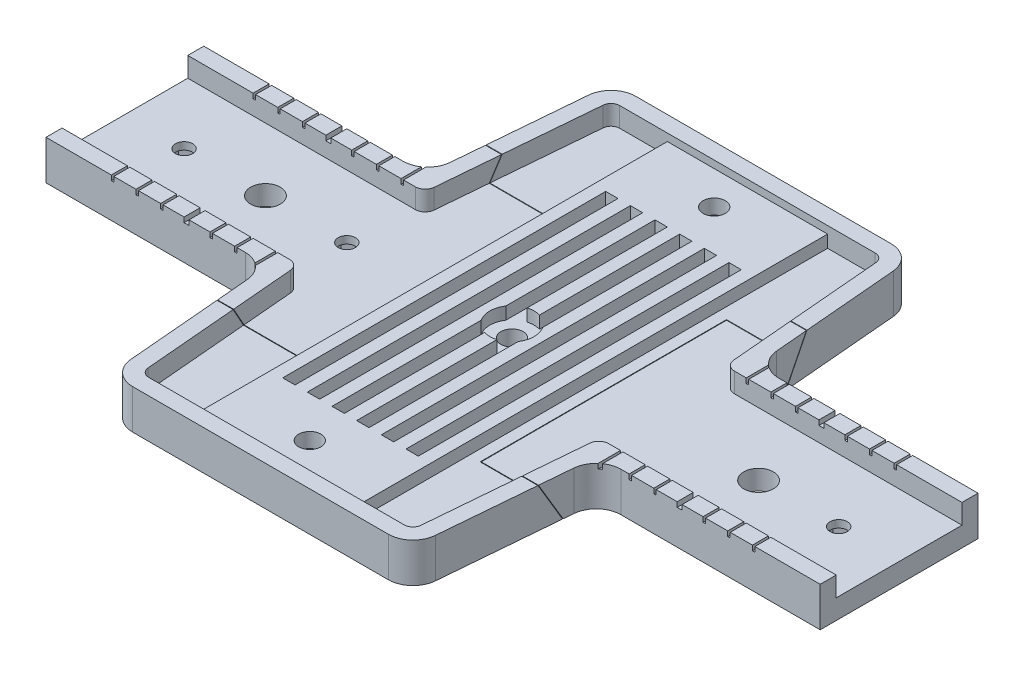
SolidWorks part; units mm, degrees
material "PBT Общее назначение"
ref_plane "Спереди" through (0, 0, 0) normal (0, 0, 1) x (1, 0, 0)
ref_plane "Сверху" through (0, 0, 0) normal (0, 1, 0) x (1, 0, 0)
ref_plane "Справа" through (0, 0, 0) normal (1, 0, 0) x (0, 0, -1)
sketch "Эскиз1" plane through (0, 0, 0) normal (0, 1, 0) x (1, 0, 0)
  line L0 (0, 0) -> (157, 0)
  line L1 (0, 0) -> (0, 32)
  line L2 (157, 0) -> (157, 32)
  line L3 (0, 32) -> (157, 32)
  dimension "D1" = 32
  dimension "D2" = 157
extrude "Бобышка-Вытянуть1" add sketch "Эскиз1" along normal blind 4
sketch "Эскиз2" plane through (0, 4, 0) normal (0, 1, 0) x (1, 0, 0)
  line L0 (0, 16) -> (157, 16) construction
  line L1 (0, 32) -> (0, 0) construction
  line L2 (157, 0) -> (157, 32) construction
  circle A0 centre (78.5, 16) radius 2.25
  dimension "D1" = 4.5
extrude "Вырез-Вытянуть1" cut sketch "Эскиз2" against normal through all
sketch "Эскиз4" plane through (0, 0, 0) normal (0, 0, 1) x (1, 0, 0)
  line L1 (78.5, 0) -> (78.5, 4) construction
  line L2 (0, 0) -> (157, 0) construction
  line L3 (0, 4) -> (157, 4) construction
  line L5 (77.25, 4) -> (79.75, 4)
  line L6 (77.25, 4) -> (77.25, 6.5)
  line L7 (79.75, 4) -> (79.75, 6.5)
  line L9 (77.25, 6.5) -> (79.75, 6.5)
  line L10 (82.25, 4) -> (84.75, 4)
  line L11 (82.25, 4) -> (82.25, 6.5)
  line L12 (84.75, 4) -> (84.75, 6.5)
  line L13 (82.25, 6.5) -> (84.75, 6.5)
  line L14 (87.25, 4) -> (89.75, 4)
  line L15 (87.25, 4) -> (87.25, 6.5)
  line L16 (89.75, 4) -> (89.75, 6.5)
  line L17 (87.25, 6.5) -> (89.75, 6.5)
  line L18 (92.25, 4) -> (94.75, 4)
  line L19 (92.25, 4) -> (92.25, 6.5)
  line L20 (94.75, 4) -> (94.75, 6.5)
  line L21 (92.25, 6.5) -> (94.75, 6.5)
  line L22 (72.25, 4) -> (74.75, 4)
  line L23 (72.25, 4) -> (72.25, 6.5)
  line L24 (74.75, 4) -> (74.75, 6.5)
  line L25 (72.25, 6.5) -> (74.75, 6.5)
  line L26 (67.25, 4) -> (69.75, 4)
  line L27 (67.25, 4) -> (67.25, 6.5)
  line L29 (69.75, 4) -> (69.75, 6.5)
  line L32 (67.25, 6.5) -> (69.75, 6.5)
  line L33 (62.25, 4) -> (64.75, 4)
  line L34 (62.25, 4) -> (62.25, 6.5)
  line L35 (64.75, 4) -> (64.75, 6.5)
  line L36 (62.25, 6.5) -> (64.75, 6.5)
  point P7 (67.5, 12)
  point P9 (85.5, 12)
  dimension "D1" = 2.5
  dimension "D2" = 2.5
  dimension "D3" = 4
  dimension "D5" = 4
  dimension "D4" = 5
  dimension "D6" = 5
extrude "Бобышка-Вытянуть3" add sketch "Эскиз4" against normal up to surface (32 mm away) up to face at (78.5, 2, -32)
ref_plane "Плоскость2" through (0, 0, 0.25) normal (0, 0, 1) x (1, 0, 0)
sketch "Эскиз7" plane through (0, 4, 0) normal (0, 1, 0) x (1, 0, 0)
  line L0 (157, 16) -> (0, 16) construction
  line L1 (157, 0) -> (157, 32) construction
  line L2 (0, 32) -> (0, 0) construction
ref_plane "Плоскость3" through (0, 0, -16) normal (0, 0, -1) x (-1, 0, 0)
sketch "Эскиз8" plane through (0, 0, 0) normal (0, -1, 0) x (1, 0, 0)
  circle A0 centre (78.5, -16) radius 2.25 construction
  circle A1 centre (78.5, -16) radius 2.25
extrude "Вырез-Вытянуть3" cut sketch "Эскиз8" against normal through all
sketch "Эскиз10" plane through (0, 4, 0) normal (0, 1, 0) x (1, 0, 0)
  line L0 (157, 0) -> (157, 3.25)
  line L1 (157, 0) -> (112, 0)
  line L2 (157, 3.25) -> (112, 3.25)
  line L3 (112, 0) -> (112, 3.25)
  line L4 (157, 0) -> (157, 32) construction
  dimension "D1" = 45
  dimension "D2" = 3.25
extrude "Бобышка-Вытянуть4" add sketch "Эскиз10" along normal blind 4
mirror "Зеркальное отражение1" about plane through (0, 0, -16) normal (0, 0, -1) of "Бобышка-Вытянуть4"
sketch "Эскиз11" plane through (0, 0, 0) normal (0, -1, 0) x (1, 0, 0)
  line L0 (140.75, 0) -> (140.75, -32) construction
  line L1 (0, 0) -> (157, 0) construction
  line L2 (157, -32) -> (0, -32) construction
  line L3 (157, 0) -> (157, -32) construction
  line L4 (16.25, 0) -> (16.25, -32) construction
  line L5 (0, -32) -> (0, 0) construction
  dimension "D1" = 16.25
  dimension "D2" = 16.25
sketch "Эскиз12" plane through (0, 6.5, 0) normal (0, 1, 0) x (1, 0, 0)
  line L0 (74.75, 32) -> (74.75, 0) construction
  line L1 (74.75, 32) -> (74.75, 0) construction
  arc A0 (79.75, 14.1292) -> (79.75, 17.8708) centre (78.5, 16) ccw construction
  arc A1 (79.75, 14.1292) -> (79.75, 17.8708) centre (78.5, 16) ccw construction
  circle A2 centre (78.5, 16) radius 4.5
  dimension "D1" = 9
extrude "Вырез-Вытянуть4" cut sketch "Эскиз12" against normal up to surface (2.5 mm away) up to face at (76.25, 4, -18.3549)
sketch "Эскиз13" plane through (0, 0, 0) normal (0, 0, 1) x (1, 0, 0)
  line L0 (78.5, 0) -> (78.5, 6.5) construction
  line L1 (0, 0) -> (157, 0) construction
  line L2 (79.75, 6.5) -> (77.25, 6.5) construction
ref_plane "Плоскость4" through (78.5, 0, 0) normal (1, 0, 0) x (0, 1, 0)
mirror "Зеркальное отражение2" about plane through (78.5, 0, 0) normal (1, 0, 0) of "Зеркальное отражение1", "Бобышка-Вытянуть4"
sketch "Эскиз14" plane through (0, 4, 0) normal (0, 1, 0) x (1, 0, 0)
  line L0 (112, 0) -> (109.392, -30.427)
  line L1 (104.4102, -35) -> (52.5898, -35)
  line L2 (47.608, -30.427) -> (45, 0)
  line L3 (94.75, 0) -> (112, 0) construction
  line L4 (45, 0) -> (112, 0)
  line L5 (78.5, 0) -> (78.5, -35) construction
  arc A0 (109.392, -30.427) -> (104.4102, -35) centre (104.4102, -30) cw
  arc A1 (52.5898, -35) -> (47.608, -30.427) centre (52.5898, -30) cw
  point P10 (78.5, -35)
  point P13 (109, -35)
  dimension "D3" = 5
  dimension "D1" = 35
  dimension "D2" = 3
extrude "Бобышка-Вытянуть5" add sketch "Эскиз14" against normal up to surface (4 mm away) up to face at (78.5, 0, -13.75)
mirror "Зеркальное отражение3" about plane through (0, 0, -16) normal (0, 0, -1) of "Бобышка-Вытянуть5"
sketch "Эскиз15" plane through (0, 4, 0) normal (0, 1, 0) x (1, 0, 0)
  line L0 (78.5, -35) -> (78.5, 67) construction
  line L1 (52.5898, -35) -> (104.4102, -35) construction
  line L2 (52.5898, 67) -> (104.4102, 67) construction
  line L6 (157, 16) -> (0, 16) construction
  line L7 (157, 16) -> (0, 16) construction
  circle A0 centre (78.5, -25) radius 2.25
  circle A1 centre (78.5, 57) radius 2.25
  dimension "D1" = 10
  dimension "D2" = 4.5
extrude "Вырез-Вытянуть5" cut sketch "Эскиз15" against normal through all
sketch "Эскиз16" plane through (78.5, 0, 0) normal (1, 0, 0) x (0, 1, 0)
  line L0 (4, 35) -> (4, 31.75)
  line L1 (4, 35) -> (8, 35)
  line L2 (4, 31.75) -> (8, 31.75)
  line L3 (8, 35) -> (8, 31.75)
  dimension "D1" = 3.25
  dimension "D2" = 4
sketch "Эскиз17" plane through (0, 4, 0) normal (0, 1, 0) x (1, 0, 0)
  line L0 (52.5898, -35) -> (104.4102, -35) construction
  line L1 (45, 0) -> (47.608, -30.427) construction
  line L2 (52.5898, -35) -> (78.5, -35)
  line L3 (44.7214, 3.25) -> (47.608, -30.427)
  line L6 (0, 3.25) -> (45, 3.25) construction
  arc A0 (47.608, -30.427) -> (52.5898, -35) centre (52.5898, -30) ccw construction
  arc A1 (47.608, -30.427) -> (52.5898, -35) centre (52.5898, -30) ccw
sweep "По траектории2" add profiles "Эскиз16" path "Эскиз17"
mirror "Зеркальное отражение4" about plane through (78.5, 0, 0) normal (1, 0, 0) of "По траектории2"
mirror "Зеркальное отражение5" about plane through (0, 0, -16) normal (0, 0, -1) of "Зеркальное отражение4", "По траектории2"
sketch "Эскиз19" plane through (0, 0, 0) normal (0, 0, 1) x (1, 0, 0)
  line L4 (82.25, 4) -> (84.75, 4)
  line L5 (84.75, 4) -> (84.75, 6.5)
  line L6 (84.75, 6.5) -> (82.25, 6.5)
  line L7 (82.25, 6.5) -> (82.25, 4)
  line L8 (82.25, 4) -> (84.75, 4)
  line L9 (84.75, 4) -> (84.75, 6.5)
  line L10 (84.75, 6.5) -> (82.25, 6.5)
  line L11 (82.25, 6.5) -> (82.25, 4)
  line L12 (72.25, 4) -> (74.75, 4)
  line L13 (74.75, 4) -> (74.75, 6.5)
  line L14 (74.75, 6.5) -> (72.25, 6.5)
  line L15 (72.25, 6.5) -> (72.25, 4)
  line L16 (72.25, 4) -> (74.75, 4)
  line L17 (74.75, 4) -> (74.75, 6.5)
  line L18 (74.75, 6.5) -> (72.25, 6.5)
  line L19 (72.25, 6.5) -> (72.25, 4)
  line L20 (92.25, 4) -> (94.75, 4)
  line L21 (94.75, 4) -> (94.75, 6.5)
  line L22 (94.75, 6.5) -> (92.25, 6.5)
  line L23 (92.25, 6.5) -> (92.25, 4)
  line L24 (92.25, 4) -> (94.75, 4)
  line L25 (94.75, 4) -> (94.75, 6.5)
  line L26 (94.75, 6.5) -> (92.25, 6.5)
  line L27 (92.25, 6.5) -> (92.25, 4)
  line L28 (87.25, 4) -> (89.75, 4)
  line L29 (87.25, 6.5) -> (87.25, 4)
  line L30 (89.75, 6.5) -> (87.25, 6.5)
  line L31 (89.75, 4) -> (89.75, 6.5)
  line L32 (87.25, 4) -> (89.75, 4)
  line L33 (87.25, 6.5) -> (87.25, 4)
  line L34 (89.75, 6.5) -> (87.25, 6.5)
  line L35 (89.75, 4) -> (89.75, 6.5)
  line L36 (77.25, 6.5) -> (77.25, 4)
  line L37 (77.25, 4) -> (79.75, 4)
  line L38 (79.75, 4) -> (79.75, 6.5)
  line L39 (79.75, 6.5) -> (77.25, 6.5)
  line L40 (77.25, 6.5) -> (77.25, 4)
  line L41 (77.25, 4) -> (79.75, 4)
  line L42 (79.75, 4) -> (79.75, 6.5)
  line L43 (79.75, 6.5) -> (77.25, 6.5)
  line L44 (62.25, 4) -> (64.75, 4)
  line L45 (64.75, 4) -> (64.75, 6.5)
  line L46 (64.75, 6.5) -> (62.25, 6.5)
  line L47 (62.25, 6.5) -> (62.25, 4)
  line L48 (62.25, 4) -> (64.75, 4)
  line L49 (64.75, 4) -> (64.75, 6.5)
  line L50 (64.75, 6.5) -> (62.25, 6.5)
  line L51 (62.25, 6.5) -> (62.25, 4)
  line L52 (67.25, 4) -> (69.75, 4)
  line L53 (69.75, 4) -> (69.75, 6.5)
  line L54 (69.75, 6.5) -> (67.25, 6.5)
  line L55 (67.25, 6.5) -> (67.25, 4)
  line L56 (67.25, 4) -> (69.75, 4)
  line L57 (69.75, 4) -> (69.75, 6.5)
  line L58 (69.75, 6.5) -> (67.25, 6.5)
  line L59 (67.25, 6.5) -> (67.25, 4)
  dimension "D1" = 0
  dimension "D2" = 0
  dimension "D3" = 0
  dimension "D4" = 0
  dimension "D5" = 0
  dimension "D6" = 0
  dimension "D7" = 0
extrude "Бобышка-Вытянуть6" add sketch "Эскиз19" along normal up to surface (31.75 mm away)
sketch "Эскиз20" plane through (0, 0, -32) normal (0, 0, -1) x (-1, 0, 0)
  line L4 (-84.75, 4) -> (-82.25, 4)
  line L5 (-84.75, 6.5) -> (-84.75, 4)
  line L6 (-82.25, 6.5) -> (-84.75, 6.5)
  line L7 (-82.25, 4) -> (-82.25, 6.5)
  line L8 (-84.75, 4) -> (-82.25, 4)
  line L9 (-84.75, 6.5) -> (-84.75, 4)
  line L10 (-82.25, 6.5) -> (-84.75, 6.5)
  line L11 (-82.25, 4) -> (-82.25, 6.5)
  line L12 (-74.75, 4) -> (-72.25, 4)
  line L13 (-74.75, 6.5) -> (-74.75, 4)
  line L14 (-72.25, 6.5) -> (-74.75, 6.5)
  line L15 (-72.25, 4) -> (-72.25, 6.5)
  line L16 (-74.75, 4) -> (-72.25, 4)
  line L17 (-74.75, 6.5) -> (-74.75, 4)
  line L18 (-72.25, 6.5) -> (-74.75, 6.5)
  line L19 (-72.25, 4) -> (-72.25, 6.5)
  line L20 (-94.75, 4) -> (-92.25, 4)
  line L21 (-94.75, 6.5) -> (-94.75, 4)
  line L22 (-92.25, 6.5) -> (-94.75, 6.5)
  line L23 (-92.25, 4) -> (-92.25, 6.5)
  line L24 (-94.75, 4) -> (-92.25, 4)
  line L25 (-94.75, 6.5) -> (-94.75, 4)
  line L26 (-92.25, 6.5) -> (-94.75, 6.5)
  line L27 (-92.25, 4) -> (-92.25, 6.5)
  line L28 (-89.75, 4) -> (-87.25, 4)
  line L29 (-87.25, 4) -> (-87.25, 6.5)
  line L30 (-87.25, 6.5) -> (-89.75, 6.5)
  line L31 (-89.75, 6.5) -> (-89.75, 4)
  line L32 (-89.75, 4) -> (-87.25, 4)
  line L33 (-87.25, 4) -> (-87.25, 6.5)
  line L34 (-87.25, 6.5) -> (-89.75, 6.5)
  line L35 (-89.75, 6.5) -> (-89.75, 4)
  line L36 (-77.25, 4) -> (-77.25, 6.5)
  line L37 (-79.75, 4) -> (-77.25, 4)
  line L38 (-79.75, 6.5) -> (-79.75, 4)
  line L39 (-77.25, 6.5) -> (-79.75, 6.5)
  line L40 (-77.25, 4) -> (-77.25, 6.5)
  line L41 (-79.75, 4) -> (-77.25, 4)
  line L42 (-79.75, 6.5) -> (-79.75, 4)
  line L43 (-77.25, 6.5) -> (-79.75, 6.5)
  line L44 (-64.75, 4) -> (-62.25, 4)
  line L45 (-64.75, 6.5) -> (-64.75, 4)
  line L46 (-62.25, 6.5) -> (-64.75, 6.5)
  line L47 (-62.25, 4) -> (-62.25, 6.5)
  line L48 (-64.75, 4) -> (-62.25, 4)
  line L49 (-64.75, 6.5) -> (-64.75, 4)
  line L50 (-62.25, 6.5) -> (-64.75, 6.5)
  line L51 (-62.25, 4) -> (-62.25, 6.5)
  line L52 (-69.75, 4) -> (-67.25, 4)
  line L53 (-69.75, 6.5) -> (-69.75, 4)
  line L54 (-67.25, 6.5) -> (-69.75, 6.5)
  line L55 (-67.25, 4) -> (-67.25, 6.5)
  line L56 (-69.75, 4) -> (-67.25, 4)
  line L57 (-69.75, 6.5) -> (-69.75, 4)
  line L58 (-67.25, 6.5) -> (-69.75, 6.5)
  line L59 (-67.25, 4) -> (-67.25, 6.5)
  dimension "D1" = 0
  dimension "D2" = 0
  dimension "D3" = 0
  dimension "D4" = 0
  dimension "D5" = 0
  dimension "D6" = 0
  dimension "D7" = 0
extrude "Бобышка-Вытянуть7" add sketch "Эскиз20" along normal up to surface (31.75 mm away)
sketch "Эскиз21" plane through (0, 4, 0) normal (0, -1, 0) x (1, 0, 0)
  circle A0 centre (78.5, 25) radius 2.25 construction
  circle A1 centre (78.5, 25) radius 2.25
  circle A2 centre (78.5, -57) radius 2.25 construction
  circle A3 centre (78.5, -57) radius 2.25
extrude "Вырез-Вытянуть6" cut sketch "Эскиз21" against normal through all
sketch "Эскиз22" plane through (0, 8, 0) normal (0, 1, 0) x (1, 0, 0)
  line L0 (106.1538, -30.1495) -> (109.0404, 3.5276) construction
  line L1 (109.0404, 3.5276) -> (112.2786, 3.25) construction
  line L3 (109.0167, 3.25) -> (109.0404, 3.5276)
  line L4 (109.0404, 3.5276) -> (112.2786, 3.25)
  line L6 (112.2786, 3.25) -> (109.0167, 3.25)
extrude "Вырез-Вытянуть7" cut sketch "Эскиз22" against normal up to surface (4 mm away) up to face at (113.9908, 4, -16)
mirror "Зеркальное отражение7" about plane through (0, 0, -16) normal (0, 0, -1) of "Вырез-Вытянуть7"
mirror "Зеркальное отражение8" about plane through (78.5, 0, 0) normal (1, 0, 0) of "Зеркальное отражение7"
sketch "Эскиз23" plane through (0, 0, 0) normal (0, -1, 0) x (1, 0, 0)
  line L2 (157, -16) -> (0, -16) construction
  circle A0 centre (28.5, -16) radius 3
  circle A1 centre (78.5, -16) radius 2.25 construction
  circle A2 centre (128.5, -16) radius 3
  dimension "D1" = 6
  dimension "D2" = 50
  dimension "D3" = 50
  dimension "D4" = 6
extrude "Вырез-Вытянуть8" cut sketch "Эскиз23" against normal through all
sketch "Эскиз24" plane through (0, 8, 0) normal (0, 1, 0) x (1, 0, 0)
  line L0 (45, 0) -> (45, 3.25)
  line L1 (0, 3.25) -> (47.9833, 3.25) construction
  line L2 (45, 3.25) -> (47.9833, 3.25)
  line L4 (52.5898, -35) -> (104.4102, -35) construction
  line L5 (104.4102, -31.75) -> (52.5898, -31.75) construction
  line L7 (50.8462, -30.1495) -> (47.9833, 3.25) construction
  line L8 (52.5898, -35) -> (104.4102, -35)
  line L9 (104.4102, -31.75) -> (52.5898, -31.75)
  line L11 (47.608, -30.427) -> (45, 0) construction
  line L12 (50.8462, -30.1495) -> (47.9833, 3.25)
  line L13 (47.608, -30.427) -> (45, 0)
  line L14 (109.392, -30.427) -> (112, 0) construction
  line L15 (106.1538, -30.1495) -> (109.0167, 3.25) construction
  line L16 (109.392, -30.427) -> (112, 0)
  line L17 (106.1538, -30.1495) -> (109.0167, 3.25)
  line L18 (157, 3.25) -> (109.0167, 3.25) construction
  line L19 (112, 3.25) -> (109.0167, 3.25)
  line L20 (112, 0) -> (112, 3.25)
  arc A0 (50.8462, -30.1495) -> (52.5898, -31.75) centre (52.5898, -30) ccw construction
  arc A1 (47.608, -30.427) -> (52.5898, -35) centre (52.5898, -30) ccw construction
  arc A2 (104.4102, -35) -> (109.392, -30.427) centre (104.4102, -30) ccw construction
  arc A3 (104.4102, -31.75) -> (106.1538, -30.1495) centre (104.4102, -30) ccw construction
  arc A4 (50.8462, -30.1495) -> (52.5898, -31.75) centre (52.5898, -30) ccw
  arc A5 (47.608, -30.427) -> (52.5898, -35) centre (52.5898, -30) ccw
  arc A6 (104.4102, -35) -> (109.392, -30.427) centre (104.4102, -30) ccw
  arc A7 (104.4102, -31.75) -> (106.1538, -30.1495) centre (104.4102, -30) ccw
extrude "Вырез-Вытянуть9" cut sketch "Эскиз24" against normal blind 2
mirror "Зеркальное отражение9" about plane through (0, 0, -16) normal (0, 0, -1) of "Вырез-Вытянуть9"
sketch "Эскиз25" plane through (0, 0, 0) normal (0, -1, 0) x (1, 0, 0)
  line L0 (78.5, 25) -> (82.5415, 25) construction
  line L1 (74.4585, 25) -> (76.4793, 21.5)
  line L2 (76.4793, 21.5) -> (80.5207, 21.5)
  line L3 (80.5207, 21.5) -> (82.5415, 25)
  line L4 (82.5415, 25) -> (80.5207, 28.5)
  line L5 (80.5207, 28.5) -> (76.4793, 28.5)
  line L6 (76.4793, 28.5) -> (74.4585, 25)
  circle A0 centre (78.5, 25) radius 3.5 construction
  dimension "D1" = 7
extrude "Вырез-Вытянуть10" cut sketch "Эскиз25" against normal blind 3.5
sketch "Эскиз26" plane through (0, 4, 0) normal (0, 1, 0) x (1, 0, 0)
  circle A0 centre (78.5, -25) radius 4
  arc A1 (79.75, -26.8708) -> (79.75, -23.1292) centre (78.5, -25) ccw construction
  arc A2 (79.75, -26.8708) -> (79.75, -23.1292) centre (78.5, -25) ccw construction
  circle A3 centre (78.5, -25) radius 2.25
  circle A4 centre (78.5, 57) radius 4
  arc A5 (77.25, 58.8708) -> (77.25, 55.1292) centre (78.5, 57) ccw construction
  arc A6 (77.25, 58.8708) -> (77.25, 55.1292) centre (78.5, 57) ccw construction
  circle A7 centre (78.5, 57) radius 2.25
  dimension "D1" = 8
  dimension "D2" = 8
extrude "Бобышка-Вытянуть8" add sketch "Эскиз26" along normal up to surface (2.5 mm away) up to face at (78.5, 6.5, 5.6755)
fillet "Скругление3" radius 1 4 edges at (74.75, 5.25, 23.6081) (74.75, 5.25, 26.3919) (82.25, 5.25, 23.6081) (82.25, 5.25, 26.3919)
fillet "Скругление4" radius 1 2 edges at (82.25, 5.25, -55.6081) (74.75, 5.25, -55.6081)
mirror "Зеркальное отражение12" about plane through (0, 0, -16) normal (0, 0, -1) of "Вырез-Вытянуть10"
sketch "Эскиз27" plane through (0, 4, 0) normal (0, 1, 0) x (1, 0, 0)
  line L0 (157, 16) -> (0, 16) construction
  line L1 (157, 3.25) -> (157, 28.75) construction
  circle A1 centre (45, 16) radius 1.75
  circle A3 centre (12, 16) radius 1.75
  circle A5 centre (144.75, 16) radius 1.75
  circle A6 centre (28.5, 16) radius 3 construction
  dimension "D1" = 3.5
  dimension "D2" = 3.5
  dimension "D3" = 16.5
  dimension "D4" = 33
  dimension "D5" = 3.5
  dimension "D6" = 12.25
extrude "Вырез-Вытянуть11" cut sketch "Эскиз27" against normal through all
sketch "Эскиз28" plane through (0, 0, 0) normal (0, -1, 0) x (1, 0, 0)
  line L0 (12, -16) -> (12, -12.8246) construction
  line L1 (12, -19.1754) -> (14.75, -17.5877)
  line L2 (14.75, -17.5877) -> (14.75, -14.4123)
  line L3 (14.75, -14.4123) -> (12, -12.8246)
  line L4 (12, -12.8246) -> (9.25, -14.4123)
  line L5 (9.25, -14.4123) -> (9.25, -17.5877)
  line L6 (9.25, -17.5877) -> (12, -19.1754)
  line L7 (45, -19.1754) -> (47.75, -17.5877)
  line L8 (47.75, -17.5877) -> (47.75, -14.4123)
  line L9 (47.75, -14.4123) -> (45, -12.8246)
  line L10 (45, -12.8246) -> (42.25, -14.4123)
  line L11 (42.25, -14.4123) -> (42.25, -17.5877)
  line L12 (42.25, -17.5877) -> (45, -19.1754)
  line L13 (45, -16) -> (45, -12.8246) construction
  line L14 (144.75, -16) -> (144.75, -12.8246) construction
  line L15 (144.75, -19.1754) -> (147.5, -17.5877)
  line L16 (147.5, -17.5877) -> (147.5, -14.4123)
  line L17 (147.5, -14.4123) -> (144.75, -12.8246)
  line L18 (144.75, -12.8246) -> (142, -14.4123)
  line L19 (142, -14.4123) -> (142, -17.5877)
  line L20 (142, -17.5877) -> (144.75, -19.1754)
  circle A0 centre (12, -16) radius 2.75 construction
  circle A1 centre (45, -16) radius 2.75 construction
  circle A2 centre (144.75, -16) radius 2.75 construction
  dimension "D1" = 5.5
  dimension "D2" = 5.5
  dimension "D3" = 5.5
extrude "Вырез-Вытянуть12" cut sketch "Эскиз28" against normal blind 2.5
sketch "Sketch2" plane through (0, 8, 0) normal (0, 1, 0) x (1, 0, 0)
  line L0 (28.5, 16) -> (28.5, 0) construction
  line L1 (45, 0) -> (0, 0) construction
  line L2 (28, 0) -> (29, 0)
  line L3 (28, 0) -> (28, 3.25)
  line L4 (29, 0) -> (29, 3.25)
  line L5 (28, 3.25) -> (29, 3.25)
  line L6 (0, 3.25) -> (47.9833, 3.25) construction
  line L7 (33.25, 3.25) -> (33.75, 3.25)
  line L8 (33.25, 3.25) -> (33.25, 0)
  line L9 (33.75, 3.25) -> (33.75, 0)
  line L10 (33.25, 0) -> (33.75, 0)
  line L11 (0, 3.25) -> (45, 3.25) construction
  line L12 (33.5, 3.25) -> (33.5, 0) construction
  line L13 (38.25, 3.25) -> (38.75, 3.25)
  line L14 (38.25, 3.25) -> (38.25, 0)
  line L15 (38.75, 3.25) -> (38.75, 0)
  line L16 (38.25, 0) -> (38.75, 0)
  line L17 (38.5, 3.25) -> (38.5, 0) construction
  line L18 (43.25, 3.25) -> (43.75, 3.25)
  line L19 (43.25, 3.25) -> (43.25, 0)
  line L20 (43.75, 3.25) -> (43.75, 0)
  line L21 (43.25, 0) -> (43.75, 0)
  line L22 (43.5, 3.25) -> (43.5, 0) construction
  line L23 (13.5, 3.25) -> (13.5, 0) construction
  line L24 (18.5, 3.25) -> (18.5, 0) construction
  line L25 (23.5, 3.25) -> (23.5, 0) construction
  line L26 (13.75, 0) -> (13.25, 0)
  line L27 (13.25, 3.25) -> (13.25, 0)
  line L28 (13.75, 3.25) -> (13.75, 0)
  line L29 (13.75, 3.25) -> (13.25, 3.25)
  line L30 (18.75, 0) -> (18.25, 0)
  line L31 (18.25, 3.25) -> (18.25, 0)
  line L32 (18.75, 3.25) -> (18.75, 0)
  line L33 (18.75, 3.25) -> (18.25, 3.25)
  line L34 (23.75, 0) -> (23.25, 0)
  line L35 (23.25, 3.25) -> (23.25, 0)
  line L36 (23.75, 3.25) -> (23.75, 0)
  line L37 (23.75, 3.25) -> (23.25, 3.25)
  circle A0 centre (28.5, 16) radius 3 construction
  circle A1 centre (28.5, 16) radius 3 construction
  dimension "D1" = 1
  dimension "D2" = 0.5
  dimension "D3" = 5
  dimension "D5" = 5
  dimension "D4" = 3
extrude "Cut-Extrude2" cut sketch "Sketch2" against normal blind 1
mirror "Mirror2" about plane through (78.5, 0, 0) normal (1, 0, 0) of "Cut-Extrude2"
mirror "Mirror3" about plane through (0, 0, -16) normal (0, 0, -1) of "Cut-Extrude2"
mirror "Mirror4" about plane through (0, 0, -16) normal (0, 0, -1) of "Mirror2"
sketch "Эскиз29" plane through (0, 0, 0) normal (-1, 0, 0) x (0, 0, 1)
  line L8 (-32, 0) -> (0, 0)
  line L9 (0, 0) -> (0, 8)
  line L10 (0, 8) -> (-3.25, 8)
  line L11 (-3.25, 8) -> (-3.25, 4)
  line L12 (-3.25, 4) -> (-28.75, 4)
  line L13 (-28.75, 4) -> (-28.75, 8)
  line L14 (-28.75, 8) -> (-32, 8)
  line L15 (-32, 8) -> (-32, 0)
  line L16 (-32, 0) -> (0, 0)
  line L17 (0, 0) -> (0, 8)
  line L18 (0, 8) -> (-3.25, 8)
  line L19 (-3.25, 8) -> (-3.25, 4)
  line L20 (-3.25, 4) -> (-28.75, 4)
  line L21 (-28.75, 4) -> (-28.75, 8)
  line L22 (-28.75, 8) -> (-32, 8)
  line L23 (-32, 8) -> (-32, 0)
  dimension "D1" = 0
sketch "Эскиз30" plane through (157, 0, 0) normal (1, 0, 0) x (0, 0, -1)
  line L8 (0, 0) -> (32, 0)
  line L9 (32, 0) -> (32, 8)
  line L10 (32, 8) -> (28.75, 8)
  line L11 (28.75, 8) -> (28.75, 4)
  line L12 (28.75, 4) -> (3.25, 4)
  line L13 (3.25, 4) -> (3.25, 8)
  line L14 (3.25, 8) -> (0, 8)
  line L15 (0, 8) -> (0, 0)
  line L16 (0, 0) -> (32, 0)
  line L17 (32, 0) -> (32, 8)
  line L18 (32, 8) -> (28.75, 8)
  line L19 (28.75, 8) -> (28.75, 4)
  line L20 (28.75, 4) -> (3.25, 4)
  line L21 (3.25, 4) -> (3.25, 8)
  line L22 (3.25, 8) -> (0, 8)
  line L23 (0, 8) -> (0, 0)
  dimension "D1" = 0
sketch "Эскиз32" plane through (0, 6.5, 0) normal (0, 1, 0) x (1, 0, 0)
  line L0 (62.25, 63.75) -> (62.25, -31.75) construction
  line L1 (62.25, 63.75) -> (62.25, 48.75)
  line L2 (94.75, 63.75) -> (94.75, -31.75) construction
  line L3 (94.75, 63.75) -> (94.75, 48.75)
  line L4 (62.25, 63.75) -> (94.75, 63.75)
  line L5 (62.25, 48.75) -> (94.75, 48.75)
  circle A0 centre (78.5, 57) radius 2.25 construction
  circle A1 centre (78.5, 57) radius 2.25
  dimension "D1" = 15
extrude "Бобышка-Вытянуть9" add sketch "Эскиз32" against normal up to surface (2.5 mm away) up to face at (144.75, 4, -14.25)
mirror "Зеркальное отражение13" about plane through (0, 0, -16) normal (0, 0, -1) of "Бобышка-Вытянуть9"
sketch "Эскиз33" plane through (0, 6, 0) normal (0, 1, 0) x (1, 0, 0)
  line L14 (47.608, 62.427) -> (45, 32)
  line L16 (45, 32) -> (45, 28.75)
  line L17 (45, 28.75) -> (47.9833, 28.75)
  line L18 (47.9833, 28.75) -> (50.8462, 62.1495)
  line L19 (52.5898, 63.75) -> (62.25, 63.75)
  line L20 (62.25, 63.75) -> (94.75, 63.75)
  line L21 (94.75, 63.75) -> (104.4102, 63.75)
  line L22 (106.1538, 62.1495) -> (109.0167, 28.75)
  line L23 (109.0167, 28.75) -> (112, 28.75)
  line L24 (112, 28.75) -> (112, 32)
  line L26 (112, 32) -> (109.392, 62.427)
  line L27 (104.4102, 67) -> (52.5898, 67)
  line L28 (47.608, 62.427) -> (45, 32)
  line L30 (45, 32) -> (45, 28.75)
  line L31 (45, 28.75) -> (47.9833, 28.75)
  line L32 (47.9833, 28.75) -> (50.8462, 62.1495)
  line L33 (52.5898, 63.75) -> (62.25, 63.75)
  line L34 (62.25, 63.75) -> (94.75, 63.75)
  line L35 (94.75, 63.75) -> (104.4102, 63.75)
  line L36 (106.1538, 62.1495) -> (109.0167, 28.75)
  line L37 (109.0167, 28.75) -> (112, 28.75)
  line L38 (112, 28.75) -> (112, 32)
  line L40 (112, 32) -> (109.392, 62.427)
  line L41 (104.4102, 67) -> (52.5898, 67)
  arc A7 (52.5898, 63.75) -> (50.8462, 62.1495) centre (52.5898, 62) ccw
  arc A8 (106.1538, 62.1495) -> (104.4102, 63.75) centre (104.4102, 62) ccw
  arc A10 (109.392, 62.427) -> (104.4102, 67) centre (104.4102, 62) ccw
  arc A11 (52.5898, 67) -> (47.608, 62.427) centre (52.5898, 62) ccw
  arc A13 (52.5898, 63.75) -> (50.8462, 62.1495) centre (52.5898, 62) ccw
  arc A14 (106.1538, 62.1495) -> (104.4102, 63.75) centre (104.4102, 62) ccw
  arc A16 (109.392, 62.427) -> (104.4102, 67) centre (104.4102, 62) ccw
  arc A17 (52.5898, 67) -> (47.608, 62.427) centre (52.5898, 62) ccw
  dimension "D1" = 0
extrude "Бобышка-Вытянуть10" add sketch "Эскиз33" along normal up to surface (2 mm away) up to face at (41, 8, -30.375)
sketch "Эскиз34" plane through (0, 6, 0) normal (0, 1, 0) x (1, 0, 0)
  line L14 (45, 3.25) -> (45, 0)
  line L16 (45, 0) -> (47.608, -30.427)
  line L17 (52.5898, -35) -> (104.4102, -35)
  line L18 (109.392, -30.427) -> (112, 0)
  line L20 (112, 0) -> (112, 3.25)
  line L21 (112, 3.25) -> (109.0167, 3.25)
  line L22 (109.0167, 3.25) -> (106.1538, -30.1495)
  line L23 (104.4102, -31.75) -> (94.75, -31.75)
  line L24 (94.75, -31.75) -> (62.25, -31.75)
  line L25 (62.25, -31.75) -> (52.5898, -31.75)
  line L26 (50.8462, -30.1495) -> (47.9833, 3.25)
  line L27 (47.9833, 3.25) -> (45, 3.25)
  line L28 (45, 3.25) -> (45, 0)
  line L30 (45, 0) -> (47.608, -30.427)
  line L31 (52.5898, -35) -> (104.4102, -35)
  line L32 (109.392, -30.427) -> (112, 0)
  line L34 (112, 0) -> (112, 3.25)
  line L35 (112, 3.25) -> (109.0167, 3.25)
  line L36 (109.0167, 3.25) -> (106.1538, -30.1495)
  line L37 (104.4102, -31.75) -> (94.75, -31.75)
  line L38 (94.75, -31.75) -> (62.25, -31.75)
  line L39 (62.25, -31.75) -> (52.5898, -31.75)
  line L40 (50.8462, -30.1495) -> (47.9833, 3.25)
  line L41 (47.9833, 3.25) -> (45, 3.25)
  arc A7 (47.608, -30.427) -> (52.5898, -35) centre (52.5898, -30) ccw
  arc A8 (104.4102, -35) -> (109.392, -30.427) centre (104.4102, -30) ccw
  arc A10 (104.4102, -31.75) -> (106.1538, -30.1495) centre (104.4102, -30) ccw
  arc A11 (50.8462, -30.1495) -> (52.5898, -31.75) centre (52.5898, -30) ccw
  arc A13 (47.608, -30.427) -> (52.5898, -35) centre (52.5898, -30) ccw
  arc A14 (104.4102, -35) -> (109.392, -30.427) centre (104.4102, -30) ccw
  arc A16 (104.4102, -31.75) -> (106.1538, -30.1495) centre (104.4102, -30) ccw
  arc A17 (50.8462, -30.1495) -> (52.5898, -31.75) centre (52.5898, -30) ccw
  dimension "D1" = 0
extrude "Бобышка-Вытянуть11" add sketch "Эскиз34" along normal up to surface (2 mm away) up to face at (41, 8, -1.625)
fillet "Скругление5" radius 5 16 edges at (43.25, 7.5, 0) (43.5, 7, 0) (43.75, 7.5, 0) (112, 4, 0) (113.75, 7.5, 0) (113.25, 7.5, 0) (113.5, 7, 0) (112, 4, -32) (43.25, 7.5, -32) (43.75, 7.5, -32) (43.5, 7, -32) (113.75, 7.5, -32) (113.5, 7, -32) (113.25, 7.5, -32) (45, 4, -32) (45, 4, 0)
sketch "Эскиз35" plane through (44.6718, 0, -3.829) normal (-0.9963, 0, 0.0854) x (0.0854, 0, 0.9963)
  line L0 (15.0516, 8) -> (15.1671, 8)
  line L1 (34.3816, 8) -> (8.4328, 8) construction
  line L2 (15.1671, 8) -> (10.5483, 0)
  line L3 (8.4328, 0) -> (34.3816, 0) construction
  line L4 (10.5483, 0) -> (10.4328, 0)
  line L5 (10.4328, 0) -> (15.0516, 8)
  dimension "D1" = 0.1
  dimension "D2" = 60
  dimension "D3" = 2
sketch "Эскиз36" plane through (0, 0, 0) normal (0, -1, 0) x (1, 0, 0)
  line L0 (45.5628, 6.5657) -> (57.5628, 6.5657)
  line L1 (45.5726, 6.6807) -> (45.5628, 6.5657) construction
  line L5 (157, -16) -> (0, -16) construction
  line L6 (157, -16) -> (0, -16) construction
  line L7 (57.5628, 6.5657) -> (57.5628, -38.5657)
  line L8 (45.5628, -38.5657) -> (57.5628, -38.5657)
  point P9 (57.5628, -16)
  dimension "D1" = 12
sweep "Вырез-По траектории1" cut profiles "Эскиз35" path "Эскиз36"
sketch "Эскиз37" plane through (113.906, 0, -9.7634) normal (0.9963, 0, -0.0854) x (-0.0854, 0, -0.9963)
  line L0 (29.0234, 0) -> (28.9079, 0)
  line L1 (52.8567, 0) -> (26.9079, 0) construction
  line L2 (28.9079, 0) -> (33.5267, 8)
  line L3 (52.8567, 8) -> (26.9079, 8) construction
  line L4 (33.5267, 8) -> (33.6422, 8)
  line L5 (33.6422, 8) -> (29.0234, 0)
  dimension "D1" = 60
  dimension "D2" = 0.1
  dimension "D3" = 2
sketch "Эскиз38" plane through (0, 0, 0) normal (0, -1, 0) x (1, 0, 0)
  line L0 (111.4372, -38.5657) -> (99.4372, -38.5657)
  line L1 (109.392, -62.427) -> (111.608, -36.573) construction
  line L2 (99.4372, -38.5657) -> (99.4372, 6.5657)
  line L3 (157, -16) -> (0, -16) construction
  line L4 (157, -16) -> (0, -16) construction
  line L5 (111.4372, 6.5657) -> (99.4372, 6.5657)
  point P10 (99.4372, -16)
  dimension "D1" = 12
sweep "Вырез-По траектории2" cut profiles "Эскиз37" path "Эскиз38"
fillet "Скругление6" radius 2 1 edges at (109.0167, 6, -28.75)
fillet "Скругление7" radius 2 1 edges at (109.0167, 6, -3.25)
fillet "Скругление8" radius 2 1 edges at (47.9833, 6, -28.75)
fillet "Скругление9" radius 2 1 edges at (47.9833, 6, -3.25)
